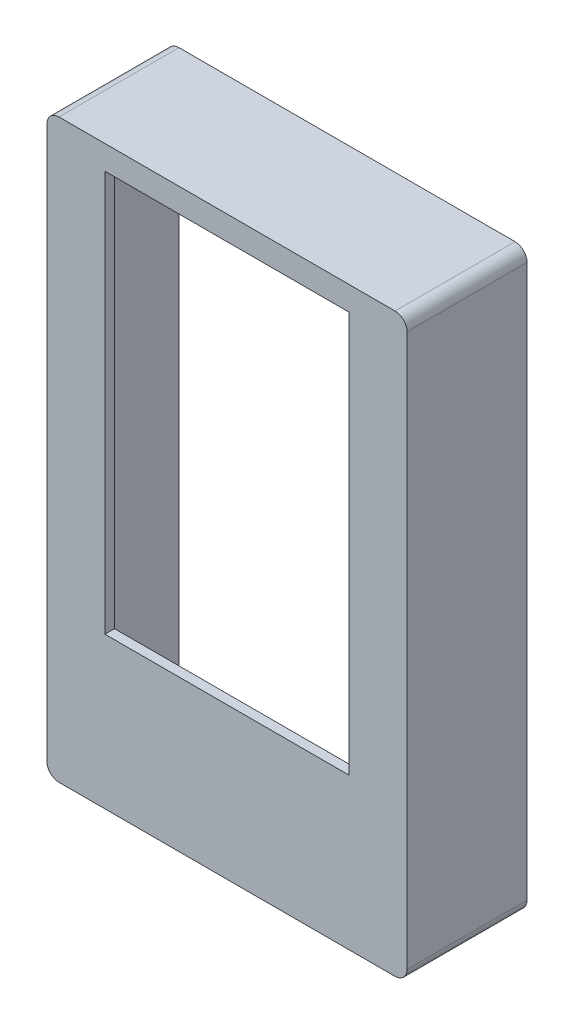
SolidWorks part; units mm, degrees
ref_plane "Plan de face" through (0, 0, 0) normal (0, 0, 1) x (1, 0, 0)
ref_plane "Plan de dessus" through (0, 0, 0) normal (0, 1, 0) x (1, 0, 0)
ref_plane "Plan de droite" through (0, 0, 0) normal (1, 0, 0) x (0, 0, -1)
sketch "Esquisse1" plane through (0, 0, 0) normal (0, 0, 1) x (1, 0, 0)
  line L1 (75, -120) -> (-75, -120)
  line L2 (75, -120) -> (75, 120)
  line L3 (75, 120) -> (-75, 120)
  line L4 (-75, -120) -> (-75, 120)
  line L5 (75, -120) -> (-75, 120) construction
  line L6 (75, 120) -> (-75, -120) construction
  point P0 (0, 0)
  dimension "D1" = 240
  dimension "D2" = 150
extrude "Boss.-Extru.1" add sketch "Esquisse1" along normal blind 50
sketch "Esquisse2" plane through (0, 0, 0) normal (0, 0, -1) x (-1, 0, 0)
  line L1 (70, -115) -> (-70, -115)
  line L2 (70, -115) -> (70, 115)
  line L3 (70, 115) -> (-70, 115)
  line L4 (-70, -115) -> (-70, 115)
  line L5 (70, -115) -> (-70, 115) construction
  line L6 (70, 115) -> (-70, -115) construction
  point P0 (0, 0)
  dimension "D1" = 5
  dimension "D2" = 5
extrude "Enlèv. mat.-Extru.1" cut sketch "Esquisse2" against normal blind 46
sketch "Esquisse3" plane through (0, 0, 50) normal (0, 0, 1) x (1, 0, 0)
  line L0 (-75, 120) -> (-50.85, 110)
  line L1 (50.85, -57) -> (-50.85, -57)
  line L2 (50.85, -57) -> (50.85, 110)
  line L3 (50.85, 110) -> (-50.85, 110)
  line L4 (-50.85, -57) -> (-50.85, 110)
  line L5 (50.85, -57) -> (-50.85, 110) construction
  line L6 (50.85, 110) -> (-50.85, -57) construction
  line L13 (50.85, 110) -> (75, 120)
  point P0 (0, 26.5)
  point P6 (0, 0)
  dimension "D1" = 167
  dimension "D2" = 101.7
  dimension "D4" = 10
extrude "Enlèv. mat.-Extru.2" cut sketch "Esquisse3" against normal through all contours L4 L1 L2 L3 region at (0, 26.5, 50)
fillet "Congé1" radius 5 4 edges at (75, -120, 25) (-75, -120, 25) (-75, 120, 25) (75, 120, 25)
